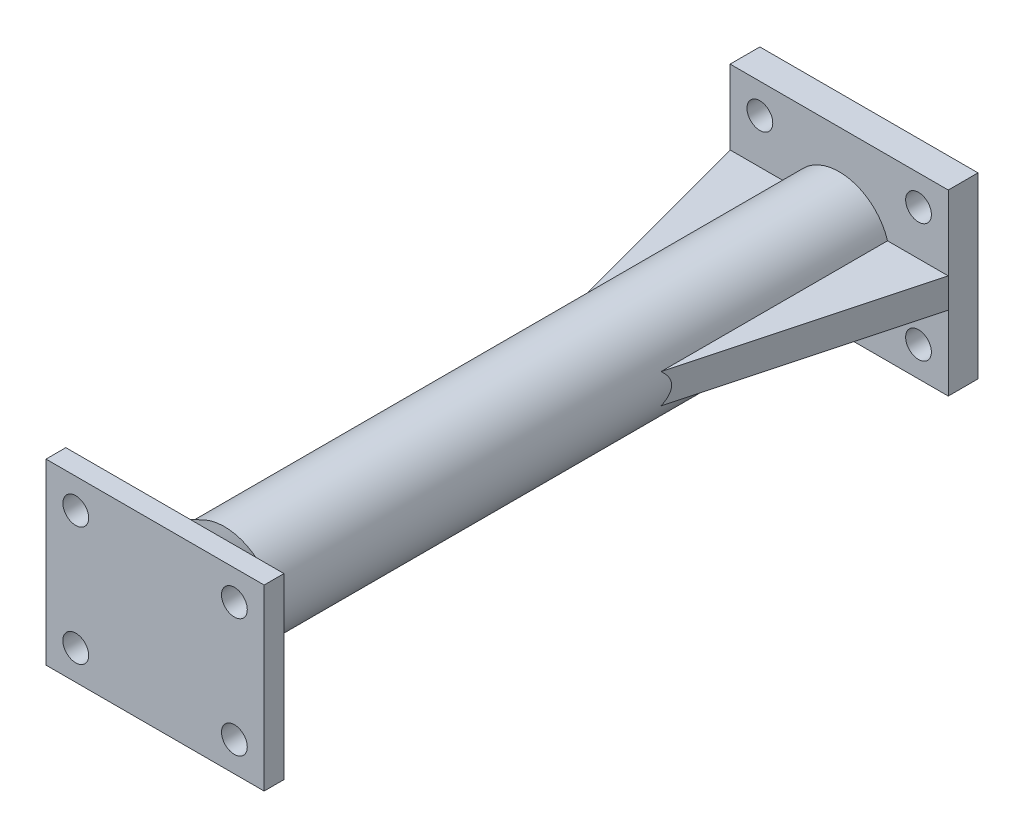
SolidWorks part; units mm, degrees
material "PMMA"
ref_plane "前视基准面" through (0, 0, 0) normal (0, 0, 1) x (1, 0, 0)
ref_plane "上视基准面" through (0, 0, 0) normal (0, 1, 0) x (1, 0, 0)
ref_plane "右视基准面" through (0, 0, 0) normal (1, 0, 0) x (0, 0, -1)
other "Configuration Table"
sketch "Sketch1" plane through (0, 0, 0) normal (0, 0, 1) x (1, 0, 0)
  line L5 (-8, 6) -> (8, 6)
  line L6 (-8, 6) -> (-8, -6)
  line L7 (-8, -6) -> (8, -6)
  line L8 (8, 6) -> (8, -6)
  line L9 (0, -6) -> (0, 6) construction
  line L10 (-8, 0) -> (8, 0) construction
  line L11 (-11, 9) -> (11, 9)
  line L12 (-11, 9) -> (-11, -9)
  line L13 (-11, -9) -> (11, -9)
  line L14 (11, 9) -> (11, -9)
  line L15 (0, -9) -> (0, 9) construction
  line L16 (-11, 0) -> (11, 0) construction
  circle A6 centre (0, 0) radius 5.1
  circle A7 centre (-8, 6) radius 1.3
  circle A8 centre (8, 6) radius 1.3
  circle A9 centre (8, -6) radius 1.3
  circle A10 centre (-8, -6) radius 1.3
  dimension "D1" = 12
  dimension "D2" = 16
  dimension "D3" = 18
  dimension "D4" = 22
extrude "Boss-Extrude1" add sketch "Sketch1" along normal blind 3 contours A6 | L14 L11 L12 L13 A10 L6 A7 L5 A8 L8 A9 L7 region at (0, 5.8, 0) region at (0, 8.7157, 0)
extrude "Boss-Extrude2" add sketch "Sketch1<3>" along normal blind 70 contours A6 region at (0, 0, 0)
sketch "Sketch1<3>" plane through (0, 0, 0) normal (0, 0, 1) x (1, 0, 0) same geometry as "Sketch1"
sketch "Sketch2" plane through (0, 0, 70) normal (0, 0, 1) x (1, 0, 0)
  line L1 (-11, 9) -> (11, 9)
  line L2 (-11, 9) -> (-11, -9)
  line L3 (-11, -9) -> (11, -9)
  line L4 (11, 9) -> (11, -9)
  line L5 (0, -9) -> (0, 9) construction
  line L6 (-11, 0) -> (11, 0) construction
  line L7 (-8, 6) -> (8, 6)
  line L8 (-8, 6) -> (-8, -6)
  line L9 (-8, -6) -> (8, -6)
  line L10 (8, 6) -> (8, -6)
  line L11 (0, -6) -> (0, 6) construction
  line L12 (-8, 0) -> (8, 0) construction
  circle A0 centre (-8, 6) radius 1.3
  circle A1 centre (8, 6) radius 1.3
  circle A2 centre (8, -6) radius 1.3
  circle A3 centre (-8, -6) radius 1.3
  point P0 (0, 0)
  point P4 (0, 0)
  circle M1 centre (0, 0) radius 5.1
  dimension "D1" = 18
  dimension "D2" = 22
  dimension "D3" = 12
  dimension "D4" = 16
extrude "Boss-Extrude3" add sketch "Sketch2" along normal blind 2 contours L4 L1 L2 L3 A3 L8 A0 L7 A1 L10 A2 L9 | A3 L9 A2 L10 A1 L7 A0 L8 M1 | M1 region at (0, 8.7157, 70) region at (0, 5.8, 70) region at (0, 0, 70)
chamfer "Chamfer2" distance 5 angle 25 1 edges at (5.1, 0, 70) first distance on face at (5.1, 0, 3)
sketch "Sketch3" plane through (0, 0, 0) normal (0, 1, 0) x (1, 0, 0)
  line L0 (-11, -3) -> (-5.1, -25)
  line L1 (-5.1, -3) -> (-5.1, -65) construction
rib "Rib2" sketch "Sketch3" sketch "Sketch3" thickness 3 extrusion direction parallel to sketch draft on no parameters "D1"=3
sketch "Sketch4" plane through (0, 0, 0) normal (0, 1, 0) x (1, 0, 0)
  line L0 (11, -3) -> (5.1, -25)
  line L1 (5.1, -65) -> (5.1, -3) construction
  line L2 (5.1, -65) -> (5.1, -3) construction
rib "Rib3" sketch "Sketch4" sketch "Sketch4" thickness 3 extrusion direction parallel to sketch draft on no parameters "D1"=3
